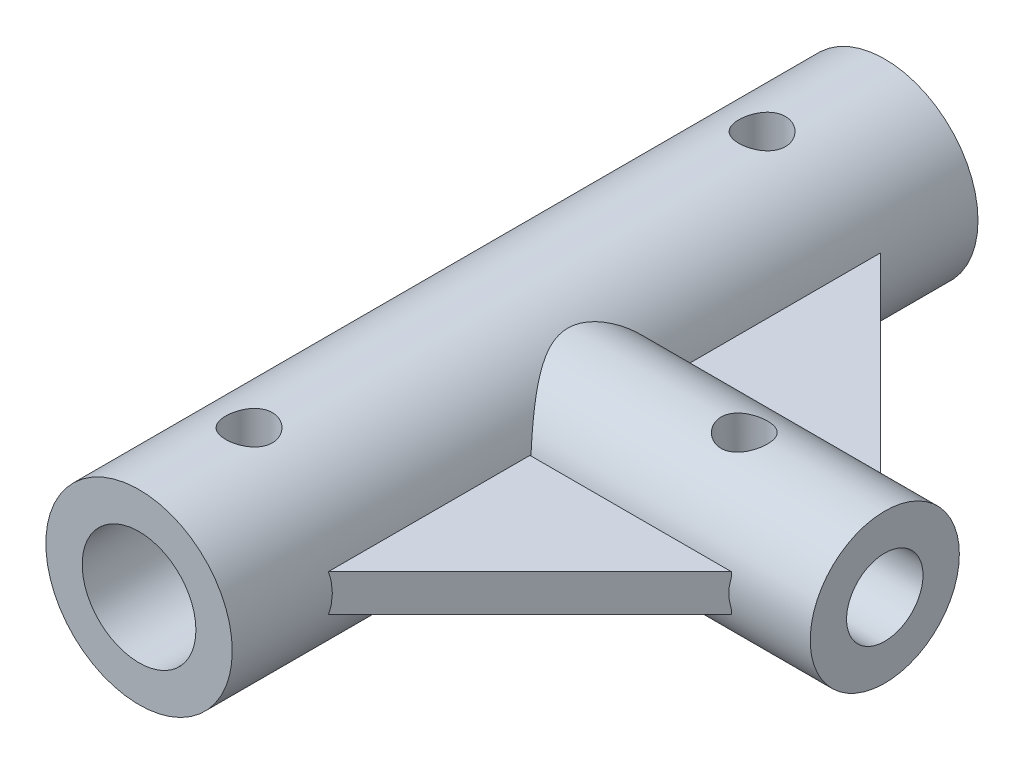
SolidWorks part; units mm, degrees
ref_plane "Front Plane" through (0, 0, 0) normal (0, 0, 1) x (1, 0, 0)
ref_plane "Top Plane" through (0, 0, 0) normal (0, 1, 0) x (1, 0, 0)
ref_plane "Right Plane" through (0, 0, 0) normal (1, 0, 0) x (0, 0, -1)
sketch "Sketch1" plane through (0, 0, 0) normal (0, 0, 1) x (1, 0, 0)
  circle A0 centre (0, 0) radius 5
  circle A1 centre (0, 0) radius 3.05
extrude "Boss-Extrude1" add sketch "Sketch1" along normal blind 20
extrude "Boss-Extrude2" add sketch "Sketch1<2>" against normal blind 20
sketch "Sketch1<2>" plane through (0, 0, 0) normal (0, 0, 1) x (1, 0, 0) same geometry as "Sketch1"
sketch "Sketch2" plane through (0, 0, 0) normal (1, 0, 0) x (0, 0, -1)
  circle A0 centre (0, 0) radius 2.05
  circle A1 centre (0, 0) radius 4
extrude "Boss-Extrude3" add sketch "Sketch2" along normal blind 20
sketch "Sketch3" plane through (20, 0, 0) normal (1, 0, 0) x (0, 0, -1)
  circle A0 centre (0, 0) radius 2.05
extrude "Cut-Extrude1" cut sketch "Sketch3" against normal blind 20
sketch "Sketch4" plane through (0, 0, 20) normal (0, 0, 1) x (1, 0, 0)
  circle A0 centre (0, 0) radius 3.05
extrude "Cut-Extrude2" cut sketch "Sketch4" against normal through all
hole_wizard "M3x0.5 Tapped Hole1" positions "3DSketch1" profile "Sketch5" tap size "M3x0.5" standard "ANSI Metric" end condition up to next
sketch3d "3DSketch1"
  point P0 (12.4888, 3.9999, 0.0232)
sketch "Sketch5" plane through (12.4888, 3.9999, 0.0232) normal (1, 0, 0) x (0, -0.0058, 1)
  line L0 (0, 0) -> (0, 1.95)
  line L1 (0, 1.95) -> (1.25, 1.95)
  line L2 (1.25, 1.95) -> (1.25, 0)
  line L5 (1.25, 0) -> (0, 0)
  line L11 (0, -6.35) -> (0, 107.95) construction
  dimension "Thru Tap Drill Dia." = 2.5
  dimension "Thru Tap Drill Depth" = 1.95
cosmetic thread "Hole Thread1" parameters "D2"=3
hole_wizard "M3x0.5 Tapped Hole2" positions "Sketch6" profile "Sketch7" tap size "M3x0.5" standard "ANSI Metric" end condition up to next
sketch "Sketch6" plane through (0, 0, 0) normal (0, 1, 0) x (1, 0, 0)
  point P0 (0, 13.4176)
  point P2 (0, -14.1007)
sketch "Sketch7" plane through (0, 0, -13.4176) normal (1, 0, 0) x (0, 0, -1)
  line L0 (0, 0) -> (0, 5)
  line L1 (0, 5) -> (1.25, 5)
  line L2 (1.25, 5) -> (1.25, 0)
  line L5 (1.25, 0) -> (0, 0)
  line L11 (0, -6.35) -> (0, 107.95) construction
  dimension "Thru Tap Drill Dia." = 2.5
  dimension "Thru Tap Drill Depth" = 5
cosmetic thread "Hole Thread2" parameters "D2"=3
cosmetic thread "Hole Thread3" parameters "D2"=3
sketch3d "3DSketch2"
  line L0 (0, 0, 20) -> (0, 0, -20) construction
  line L1 (0, 0, 20) -> (0, 0, -20) construction
  line L2 (0, 0, 20) -> (0, 0, -20) construction
  line L3 (0, 0, 20) -> (21.3154, 0, 20) construction
  line L4 (20, 0, 0) -> (20, 0, 4) construction
  line L5 (20, 0, 0) -> (3.05, 0, 0) construction
  line L6 (20, 0, 0) -> (5, 0, 0) construction
  line L7 (5, 0, 15) -> (16, 0, 4)
  line L8 (16, 0, -4) -> (5, 0, -15)
  line L9 (0, 0, -20) -> (5, 0, -20) construction
  line L10 (5, 0, -20) -> (5, 0, 20) construction
  line L11 (20, 0, 0) -> (20, 0, -4) construction
  line L12 (20, 0, -4) -> (14.5819, 0, -4) construction
  line L13 (20, 0, 4) -> (14.5799, 0, 4) construction
  line L14 (16, 0, 4) -> (5, 0, 4)
  line L15 (5, 0, 4) -> (5, 0, 15)
  line L16 (16, 0, -4) -> (5, 0, -4)
  line L17 (5, 0, -4) -> (5, 0, -15)
  circle A0 centre (0, 0, -20) radius 5 construction
  circle A1 centre (0, 0, 20) radius 5 construction
  circle A2 centre (20, 0, 0) radius 4 construction
  point P16 (0, 0, -15)
  point P20 (0, 0, 25)
  point P26 (24, 0, 0)
ref_plane "Plane1" through (0, 0, 0) normal (0, -1, 0) x (-1, 0, 0)
sketch "Sketch11" plane through (0, 0, 0) normal (0, -1, 0) x (-1, 0, 0)
  line L0 (-4.7024, -14.9302) -> (-4.7024, -3.9302)
  line L1 (-4.7024, -3.9302) -> (-15.7024, -3.9302)
  line L2 (-15.7024, -3.9302) -> (-4.7024, -14.9302)
  line L3 (-4.7024, 4.0698) -> (-4.7024, 15.0698)
  line L4 (-4.7024, 15.0698) -> (-15.7024, 4.0698)
  line L5 (-15.7024, 4.0698) -> (-4.7024, 4.0698)
  point P6 (0, 0)
extrude "Boss-Extrude4" add sketch "Sketch11" against normal mid plane 2 separate body
